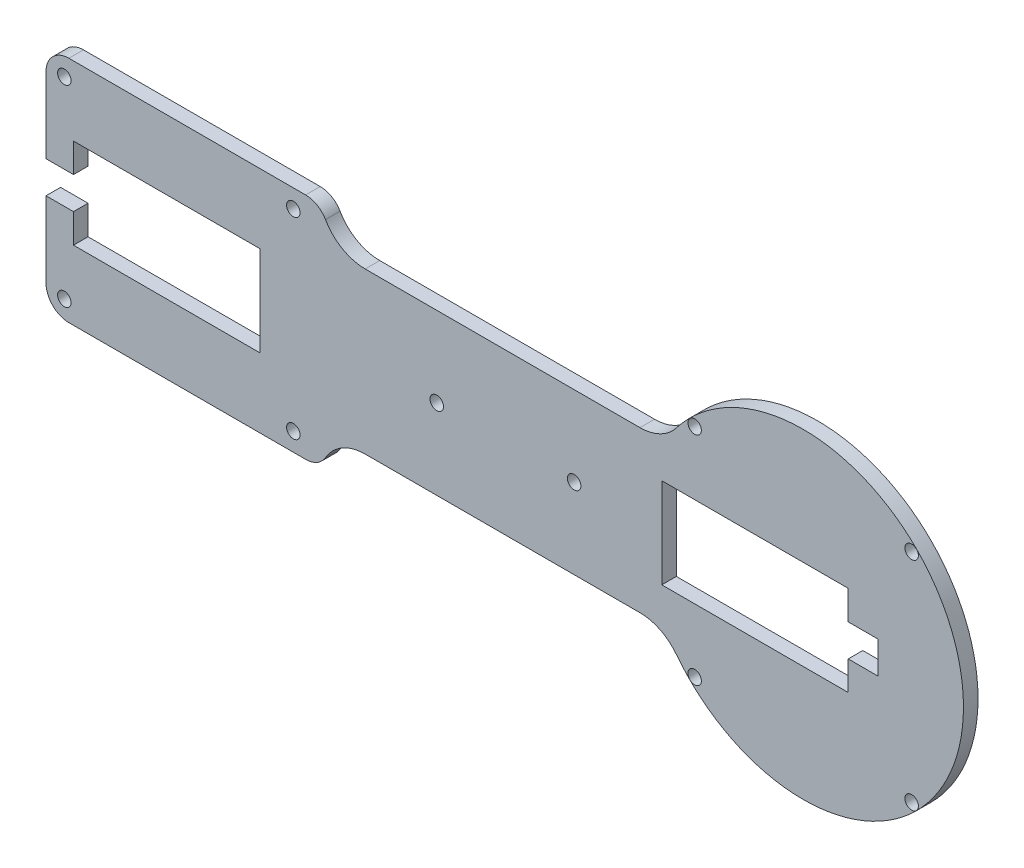
SolidWorks part; units mm, degrees
ref_plane "Front Plane" through (0, 0, 0) normal (0, 0, 1) x (1, 0, 0)
ref_plane "Top Plane" through (0, 0, 0) normal (0, 1, 0) x (1, 0, 0)
ref_plane "Right Plane" through (0, 0, 0) normal (1, 0, 0) x (0, 0, -1)
sketch "Sketch1" plane through (0, 0, 0) normal (0, 0, 1) x (1, 0, 0)
  line L1 (-105.3109, 17.5) -> (-30.3109, 17.5)
  line L2 (-105.3109, 17.5) -> (-105.3109, -17.5)
  line L3 (-105.3109, -17.5) -> (-30.3109, -17.5)
  line L5 (-105.3109, 17.5) -> (-30.3109, -17.5) construction
  line L6 (-105.3109, -17.5) -> (-30.3109, 17.5) construction
  arc A0 (-30.3109, -17.5) -> (-30.3109, 17.5) centre (0, 0) ccw
  point P4 (-67.8109, 0)
  dimension "D1" = 70
  dimension "D2" = 75
  dimension "D3" = 35
extrude "Boss-Extrude1" add sketch "Sketch1" along normal blind 3.18
fillet "Fillet1" radius 10 2 edges at (-30.3109, 17.5, 1.59) (-30.3109, -17.5, 1.59)
sketch "Sketch2" plane through (-105.3109, 0, 0) normal (-1, 0, 0) x (0, 0, 1)
  line L0 (3.18, 17.5) -> (3.18, -17.5) construction
  line L1 (3.18, -25) -> (0, -25)
  line L2 (3.18, -25) -> (3.18, 25)
  line L3 (3.18, 25) -> (0, 25)
  line L4 (0, -25) -> (0, 25)
  line L5 (3.18, -25) -> (0, 25) construction
  line L6 (3.18, 25) -> (0, -25) construction
  line L9 (0, 0) -> (5.297, 0) construction
  point P0 (1.59, 0)
  dimension "D1" = 3.18
  dimension "D2" = 50
extrude "Boss-Extrude2" add sketch "Sketch2" along normal blind 60
fillet "Fillet3" radius 10 2 edges at (-105.3109, -17.5, 1.59) (-105.3109, 17.5, 1.59)
fillet "Fillet4" radius 5 4 edges at (-105.3109, 25, 1.59) (-165.3109, 25, 1.59) (-165.3109, -25, 1.59) (-105.3109, -25, 1.59)
sketch "Sketch3" plane through (0, 0, 0) normal (0, 0, -1) x (-1, 0, 0)
  line L0 (165.3109, 20) -> (165.3109, -20) construction
  line L1 (-9.8391, 9.845) -> (30.8609, 9.845)
  line L2 (-9.8391, 9.845) -> (-9.8391, -9.845)
  line L3 (-9.8391, -9.845) -> (30.8609, -9.845)
  line L4 (30.8609, 9.845) -> (30.8609, -9.845)
  line L5 (-9.8391, 9.845) -> (30.8609, -9.845) construction
  line L6 (-9.8391, -9.845) -> (30.8609, 9.845) construction
  point P0 (10.5109, 0)
  dimension "D1" = 40.7
  dimension "D2" = 19.69
  dimension "D3" = 134.45
extrude "Cut-Extrude1" cut sketch "Sketch3" against normal through all
sketch "Sketch4" plane through (0, 0, 0) normal (0, 0, -1) x (-1, 0, 0)
  line L0 (165.3109, 20) -> (165.3109, -20) construction
  line L1 (159.3109, 9.845) -> (118.6109, 9.845)
  line L2 (159.3109, 9.845) -> (159.3109, -9.845)
  line L3 (159.3109, -9.845) -> (118.6109, -9.845)
  line L4 (118.6109, 9.845) -> (118.6109, -9.845)
  line L5 (159.3109, 9.845) -> (118.6109, -9.845) construction
  line L6 (159.3109, -9.845) -> (118.6109, 9.845) construction
  point P0 (138.9609, 0)
  dimension "D1" = 40.7
  dimension "D2" = 19.69
  dimension "D3" = 6
extrude "Cut-Extrude2" cut sketch "Sketch4" against normal blind 3.18
sketch "Sketch5" plane through (0, 0, 0) normal (0, 0, -1) x (-1, 0, 0)
  line L0 (0, 0) -> (0, 35) construction
  line L1 (0, 0) -> (23.6881, 23.6881) construction
  circle A0 centre (23.6881, 23.6881) radius 1.47
  arc A5 (27.7041, 21.3889) -> (27.7041, -21.3889) centre (0, 0) ccw construction
  dimension "D1" = 2.94
  dimension "D2" = 45
  dimension "D7" = 33.5
extrude "Cut-Extrude3" cut sketch "Sketch5" against normal blind 3.18
pattern_circular "CirPattern1" count 4 over 360 about axis through (0, 0, 3.18) along (0, 0, -1) of "Cut-Extrude3" reverse direction yes
sketch "Sketch6" plane through (0, 0, 0) normal (0, 0, -1) x (-1, 0, 0)
  line L0 (160.3109, -25) -> (108.6188, -25) construction
  line L1 (165.3109, 20) -> (165.3109, -20) construction
  circle A0 centre (161.3109, -21) radius 1.47
  circle A1 centre (111.3109, -21) radius 1.47
  dimension "D1" = 2.94
  dimension "D3" = 4
  dimension "D4" = 50
  dimension "D2" = 4
extrude "Cut-Extrude4" cut sketch "Sketch6" against normal blind 3.18
mirror "Mirror1" about plane through (0, 0, 0) normal (0, 1, 0) of "Cut-Extrude4"
sketch "Sketch7" plane through (0, 0, 0) normal (0, 0, -1) x (-1, 0, 0)
  line L0 (118.6109, 9.845) -> (118.6109, -9.845) construction
  line L1 (118.6109, 0) -> (84.9162, 0) construction
  line L2 (159.3109, -9.845) -> (159.3109, 9.845) construction
  line L3 (164.0109, -5.08) -> (164.0109, 5.08) construction
  circle A0 centre (113.9109, -5.08) radius 1.5
  circle A1 centre (113.9109, 5.08) radius 1.5
  circle A2 centre (164.0109, -5.08) radius 1.5
  circle A3 centre (164.0109, 5.08) radius 1.5
  dimension "D1" = 3
  dimension "D4" = 3
  dimension "D5" = 4.7
  dimension "D2" = 4.7
  dimension "D3" = 5.08
extrude "Cut-Extrude5" [suppressed] cut sketch "Sketch7" against normal blind 3.18
sketch "Sketch8" plane through (0, 0, 0) normal (0, 0, -1) x (-1, 0, 0)
  line L0 (95.6284, -17.5) -> (35.6195, -17.5) construction
  circle A0 centre (80, 0) radius 1.47
  circle A1 centre (50, 0) radius 1.47
  dimension "D1" = 2.94
  dimension "D2" = 30
  dimension "D4" = 17.5
  dimension "D3" = 50
extrude "Cut-Extrude6" cut sketch "Sketch8" against normal blind 3.18
sketch "Sketch9" plane through (0, 0, 0) normal (0, 0, -1) x (-1, 0, 0)
  line L0 (30.8609, -9.845) -> (30.8609, 9.845) construction
  line L1 (30.8609, 0) -> (44.7816, 0) construction
  line L2 (-9.8391, 9.845) -> (-9.8391, -9.845) construction
  circle A0 centre (35.5609, -5.08) radius 1.5
  circle A1 centre (35.5609, 5.08) radius 1.5
  circle A2 centre (-14.5391, -5.08) radius 1.5
  circle A3 centre (-14.5391, 5.08) radius 1.5
  dimension "D1" = 3
  dimension "D2" = 4.7
  dimension "D3" = 10.16
  dimension "D5" = 4.7
  dimension "D4" = 10.16
extrude "Cut-Extrude7" [suppressed] cut sketch "Sketch9" against normal blind 3.18
sketch "Sketch10" plane through (0, 0, 0) normal (0, 0, -1) x (-1, 0, 0)
  line L0 (159.3109, -9.845) -> (159.3109, 9.845) construction
  line L1 (165.8109, -3.5) -> (159.3109, -3.5)
  line L2 (165.8109, -3.5) -> (165.8109, 3.5)
  line L3 (165.8109, 3.5) -> (159.3109, 3.5)
  line L4 (159.3109, -3.5) -> (159.3109, 3.5)
  line L5 (165.8109, -3.5) -> (159.3109, 3.5) construction
  line L6 (165.8109, 3.5) -> (159.3109, -3.5) construction
  line L9 (165.3109, 0) -> (159.3109, 0) construction
  line L10 (165.3109, 20) -> (165.3109, -20) construction
  point P0 (162.5609, 0)
  dimension "D1" = 6.5
  dimension "D2" = 7
extrude "Cut-Extrude8" cut sketch "Sketch10" against normal blind 3.18
sketch "Sketch11" plane through (0, 0, 0) normal (0, 0, -1) x (-1, 0, 0)
  line L0 (-9.8391, 9.845) -> (-9.8391, -9.845) construction
  line L1 (-16.3391, -3.5) -> (-9.8391, -3.5)
  line L2 (-16.3391, -3.5) -> (-16.3391, 3.5)
  line L3 (-16.3391, 3.5) -> (-9.8391, 3.5)
  line L4 (-9.8391, -3.5) -> (-9.8391, 3.5)
  line L5 (-16.3391, -3.5) -> (-9.8391, 3.5) construction
  line L6 (-16.3391, 3.5) -> (-9.8391, -3.5) construction
  point P0 (-13.0891, 0)
  dimension "D1" = 6.5
  dimension "D2" = 7
extrude "Cut-Extrude9" cut sketch "Sketch11" against normal blind 3.18
